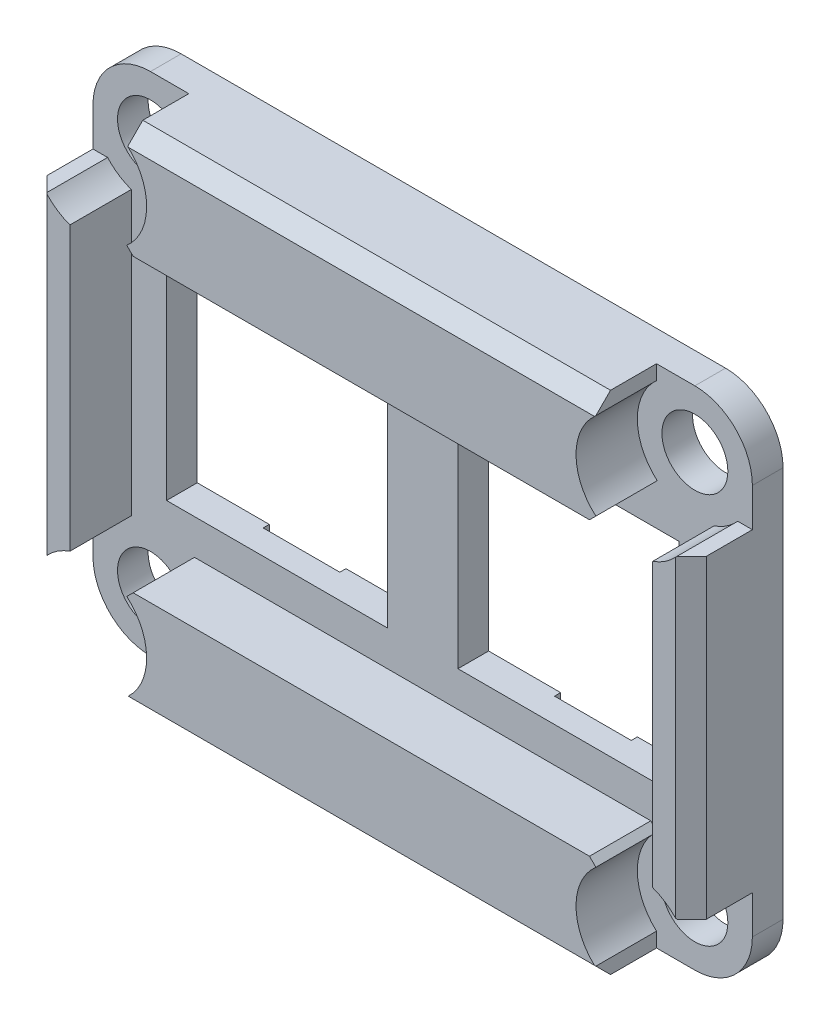
SolidWorks part; units mm, degrees
ref_plane "Спереди" through (0, 0, 0) normal (0, 0, 1) x (1, 0, 0)
ref_plane "Сверху" through (0, 0, 0) normal (0, 1, 0) x (1, 0, 0)
ref_plane "Справа" through (0, 0, 0) normal (1, 0, 0) x (0, 0, -1)
sketch "Эскиз1" plane through (0, 0, 0) normal (0, 0, 1) x (1, 0, 0)
  line L0 (0, 0) -> (0, 16.5) construction
  line L2 (-16.7, 7.2) -> (-2.3, 7.2)
  line L3 (-16.7, 7.2) -> (-16.7, -7.2)
  line L4 (17.75, 16.5) -> (-17.75, 16.5)
  line L5 (-21.5, 12.75) -> (-21.5, -12.75)
  line L6 (-17.75, -16.5) -> (17.75, -16.5)
  line L7 (21.5, -12.75) -> (21.5, 12.75)
  line L8 (17.75, 16.5) -> (-17.75, 16.5)
  line L9 (-21.5, 12.75) -> (-21.5, -12.75)
  line L10 (-17.75, -16.5) -> (17.75, -16.5)
  line L11 (21.5, -12.75) -> (21.5, 12.75)
  line L12 (-16.7, -7.2) -> (-2.3, -7.2)
  line L13 (-2.3, 7.2) -> (-2.3, -7.2)
  line L22 (2.3, 7.2) -> (2.3, -7.2)
  line L23 (16.7, -7.2) -> (2.3, -7.2)
  line L24 (16.7, 7.2) -> (16.7, -7.2)
  line L25 (16.7, 7.2) -> (2.3, 7.2)
  circle A0 centre (-17.75, 12.75) radius 2.15
  circle A1 centre (17.75, 12.75) radius 2.15
  circle A2 centre (-17.75, -12.75) radius 2.15
  circle A3 centre (17.75, -12.75) radius 2.15
  arc A4 (21.5, 12.75) -> (17.75, 16.5) centre (17.75, 12.75) ccw
  arc A5 (-17.75, 16.5) -> (-21.5, 12.75) centre (-17.75, 12.75) ccw
  arc A6 (-21.5, -12.75) -> (-17.75, -16.5) centre (-17.75, -12.75) ccw
  arc A7 (17.75, -16.5) -> (21.5, -12.75) centre (17.75, -12.75) ccw
  arc A8 (21.5, 12.75) -> (17.75, 16.5) centre (17.75, 12.75) ccw
  arc A9 (-17.75, 16.5) -> (-21.5, 12.75) centre (-17.75, 12.75) ccw
  arc A10 (-21.5, -12.75) -> (-17.75, -16.5) centre (-17.75, -12.75) ccw
  arc A11 (17.75, -16.5) -> (21.5, -12.75) centre (17.75, -12.75) ccw
  point P24 (-2.3, 0)
  dimension "D2" = 4.3
  dimension "D3" = 14.4
  dimension "D4" = 19
  dimension "D1" = 0
extrude "Бобышка-Вытянуть1" add sketch "Эскиз1" along normal blind 6
sketch "Эскиз2" plane through (0, 0, 6) normal (0, 0, 1) x (1, 0, 0)
  line L0 (-21.5, 10.25) -> (-20.5451, 10.25)
  line L1 (-21.5, 12.75) -> (-21.5, -12.75) construction
  line L2 (-21.5, 10.25) -> (-21.5, 12.75)
  line L3 (-15.25, 15.5451) -> (-15.25, 16.5)
  line L4 (17.75, 16.5) -> (-17.75, 16.5) construction
  line L5 (-15.25, 16.5) -> (-17.75, 16.5)
  line L6 (0, 16.5) -> (0, 0) construction
  line L7 (0, 0) -> (21.5, 0) construction
  line L8 (21.5, -12.75) -> (21.5, 12.75) construction
  line L9 (15.25, 16.5) -> (17.75, 16.5)
  line L10 (15.25, 15.5451) -> (15.25, 16.5)
  line L11 (21.5, 10.25) -> (21.5, 12.75)
  line L12 (21.5, 10.25) -> (20.5451, 10.25)
  line L13 (21.5, -10.25) -> (20.5451, -10.25)
  line L14 (21.5, -10.25) -> (21.5, -12.75)
  line L15 (15.25, -15.5451) -> (15.25, -16.5)
  line L16 (15.25, -16.5) -> (17.75, -16.5)
  line L17 (-15.25, -16.5) -> (-17.75, -16.5)
  line L18 (-15.25, -15.5451) -> (-15.25, -16.5)
  line L19 (-21.5, -10.25) -> (-21.5, -12.75)
  line L20 (-21.5, -10.25) -> (-20.5451, -10.25)
  line L21 (-15.8792, 9.5) -> (15.8792, 9.5)
  line L23 (-15.8792, -9.5) -> (15.8792, -9.5)
  line L31 (-19, -9.2145) -> (-19, 9.2145)
  line L32 (19, -9.2145) -> (19, 9.2145)
  arc A1 (-20.5451, 10.25) -> (-19, 9.2145) centre (-17.75, 12.75) ccw
  arc A2 (-17.75, 16.5) -> (-21.5, 12.75) centre (-17.75, 12.75) ccw construction
  arc A6 (-15.8792, 9.5) -> (-15.25, 15.5451) centre (-17.75, 12.75) ccw
  arc A7 (15.8792, 9.5) -> (15.25, 15.5451) centre (17.75, 12.75) cw
  arc A8 (15.8792, -9.5) -> (15.25, -15.5451) centre (17.75, -12.75) ccw
  arc A9 (-17.75, 16.5) -> (-21.5, 12.75) centre (-17.75, 12.75) ccw
  arc A10 (17.75, 16.5) -> (21.5, 12.75) centre (17.75, 12.75) cw
  arc A11 (20.5451, 10.25) -> (19, 9.2145) centre (17.75, 12.75) cw
  arc A12 (20.5451, -10.25) -> (19, -9.2145) centre (17.75, -12.75) ccw
  arc A13 (17.75, -16.5) -> (21.5, -12.75) centre (17.75, -12.75) ccw
  arc A14 (-17.75, -16.5) -> (-21.5, -12.75) centre (-17.75, -12.75) cw
  arc A15 (-20.5451, -10.25) -> (-19, -9.2145) centre (-17.75, -12.75) cw
  arc A16 (-15.8792, -9.5) -> (-15.25, -15.5451) centre (-17.75, -12.75) cw
  dimension "D1" = 2.5
  dimension "D2" = 19
  dimension "D3" = 19
extrude "Вырез-Вытянуть1" cut sketch "Эскиз2" against normal offset from surface (4 mm away) 2 up to face at (-9.5, 0, 0)
chamfer "Фаска1" distance 1 angle 45 8 edges at (15.8792, 9.5, 4) (15.8792, -9.5, 4) (-15.8792, -9.5, 4) (-15.8792, 9.5, 4) (21.5, 0, 6) (0, -16.5, 6) (-21.5, 0, 6) (0, 16.5, 6)
sketch "Эскиз4" plane through (0, 0, 0) normal (0, 0, -1) x (-1, 0, 0)
  line L0 (16.7, -7.2) -> (2.3, -7.2) construction
  line L1 (12, -7.2) -> (7, -7.2)
  line L2 (12, -7.2) -> (12, -8.2)
  line L3 (12, -8.2) -> (7, -8.2)
  line L4 (7, -7.2) -> (7, -8.2)
  line L5 (16.7, 0) -> (0, 0) construction
  line L6 (16.7, 7.2) -> (16.7, -7.2) construction
  line L7 (0, 0) -> (0, -16.5) construction
  line L8 (17.75, -16.5) -> (-17.75, -16.5) construction
  line L9 (7, 7.2) -> (7, 8.2)
  line L10 (12, 8.2) -> (7, 8.2)
  line L11 (12, 7.2) -> (12, 8.2)
  line L12 (12, 7.2) -> (7, 7.2)
  line L13 (-12, 7.2) -> (-7, 7.2)
  line L14 (-12, 7.2) -> (-12, 8.2)
  line L15 (-12, 8.2) -> (-7, 8.2)
  line L16 (-7, 7.2) -> (-7, 8.2)
  line L17 (-7, -7.2) -> (-7, -8.2)
  line L18 (-12, -8.2) -> (-7, -8.2)
  line L19 (-12, -7.2) -> (-12, -8.2)
  line L20 (-12, -7.2) -> (-7, -7.2)
  point P7 (9.5, -7.2)
  dimension "D1" = 1
  dimension "D2" = 5
extrude "Вырез-Вытянуть2" cut sketch "Эскиз4" against normal offset from surface (0.4 mm away) 1.6 up to face at (-15.6, 12.75, 2)
